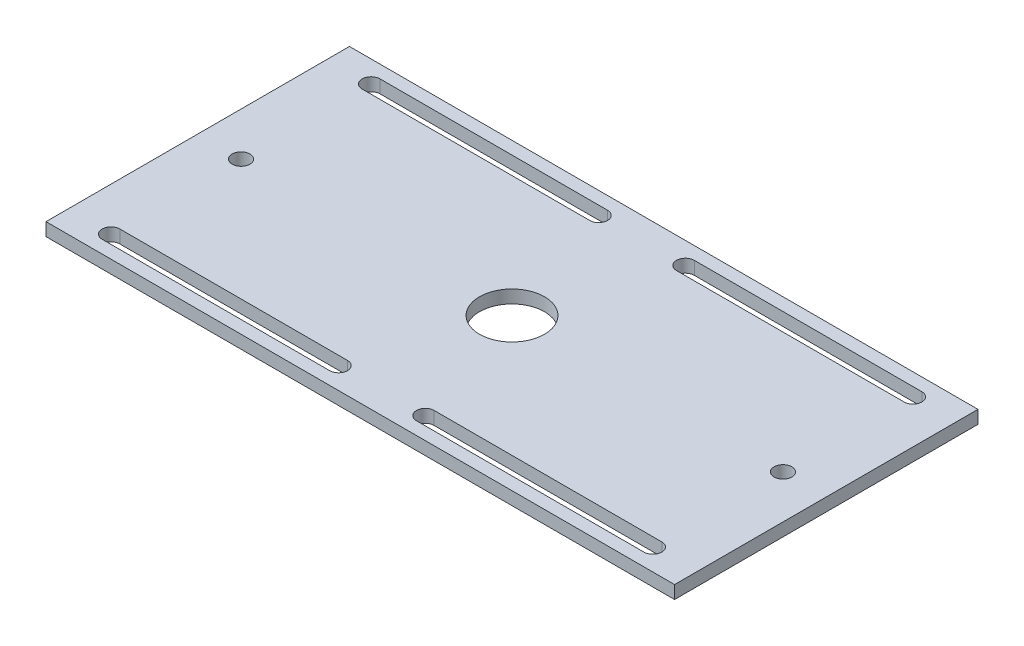
SolidWorks part; units mm, degrees
ref_plane "Спереди" through (0, 0, 0) normal (0, 0, 1) x (1, 0, 0)
ref_plane "Сверху" through (0, 0, 0) normal (0, 1, 0) x (1, 0, 0)
ref_plane "Справа" through (0, 0, 0) normal (1, 0, 0) x (0, 0, -1)
sketch "Эскиз1" plane through (0, 0, 0) normal (0, 1, 0) x (1, 0, 0)
  line L0 (0, 71.4287) -> (0, -61.4668) construction
  line L1 (-145, 70) -> (145, 70)
  line L2 (-145, 70) -> (-145, -70)
  line L3 (-145, -70) -> (145, -70)
  line L4 (145, 70) -> (145, -70)
  line L5 (-145, 70) -> (145, -70) construction
  line L6 (-145, -70) -> (145, 70) construction
  line L7 (-159.4957, 0) -> (166.2783, 0) construction
  line L8 (-163.7347, 60) -> (56.6685, 60) construction
  line L9 (-72.5, 92.4692) -> (-72.5, -67.0228) construction
  line L10 (-125, 64.1) -> (-20, 64.1)
  line L11 (-125, 55.9) -> (-20, 55.9)
  line L12 (-125, -55.9) -> (-20, -55.9)
  line L13 (-125, -64.1) -> (-20, -64.1)
  line L14 (125, -64.1) -> (20, -64.1)
  line L15 (125, -55.9) -> (20, -55.9)
  line L16 (125, 55.9) -> (20, 55.9)
  line L17 (125, 64.1) -> (20, 64.1)
  arc A0 (-125, 64.1) -> (-125, 55.9) centre (-125, 60) ccw
  arc A1 (-20, 64.1) -> (-20, 55.9) centre (-20, 60) cw
  arc A2 (-20, -64.1) -> (-20, -55.9) centre (-20, -60) ccw
  arc A3 (-125, -64.1) -> (-125, -55.9) centre (-125, -60) cw
  arc A4 (125, -64.1) -> (125, -55.9) centre (125, -60) ccw
  arc A5 (20, -64.1) -> (20, -55.9) centre (20, -60) cw
  arc A6 (20, 64.1) -> (20, 55.9) centre (20, 60) ccw
  arc A7 (125, 64.1) -> (125, 55.9) centre (125, 60) cw
  circle A8 centre (-125, 0) radius 4.1
  circle A9 centre (125, 0) radius 4.1
  circle A10 centre (0, 0) radius 15
  point P0 (0, 0)
extrude "Бобышка-Вытянуть1" add sketch "Эскиз1" along normal blind 6
